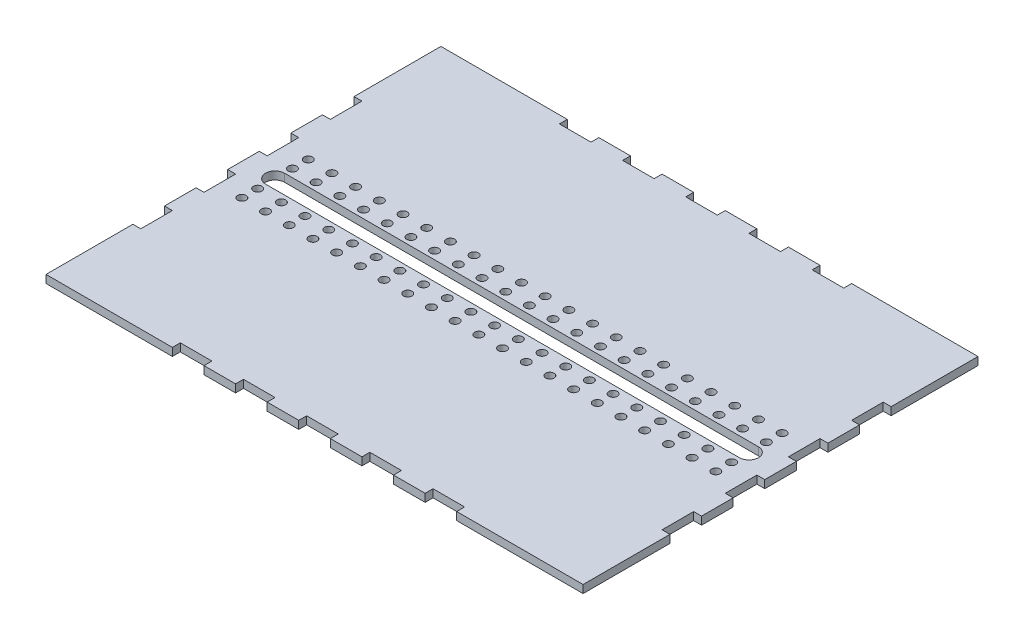
SolidWorks part; units mm, degrees
ref_plane "Front Plane" through (0, 0, 0) normal (0, 0, 1) x (1, 0, 0)
ref_plane "Top Plane" through (0, 0, 0) normal (0, 1, 0) x (1, 0, 0)
ref_plane "Right Plane" through (0, 0, 0) normal (1, 0, 0) x (0, 0, -1)
sketch "Sketch1" plane through (0, 0, 0) normal (0, 1, 0) x (1, 0, 0)
  line L0 (-14.0646, -39.6932) -> (-14.0646, 76.1041) construction
  line L3 (-122.0146, 89.7166) -> (-71.2146, 89.7166)
  line L5 (43.0854, -69.0334) -> (93.8854, -69.0334)
  line L6 (-122.0146, 89.7166) -> (93.8854, -69.0334) construction
  line L7 (-122.0146, 10.3416) -> (53.3287, 10.3416) construction
  line L8 (-20.4146, 89.7166) -> (-20.4146, 86.5416)
  line L9 (-20.4146, 86.5416) -> (-7.7146, 86.5416)
  line L10 (-7.7146, 86.5416) -> (-7.7146, 89.7166)
  line L11 (-33.1146, 89.7166) -> (-33.1146, 86.5416)
  line L12 (-33.1146, 86.5416) -> (-45.8146, 86.5416)
  line L13 (-45.8146, 86.5416) -> (-45.8146, 89.7166)
  line L14 (-58.5146, 89.7166) -> (-58.5146, 86.5416)
  line L15 (-58.5146, 86.5416) -> (-71.2146, 86.5416)
  line L16 (-71.2146, 86.5416) -> (-71.2146, 89.7166)
  line L17 (-58.5146, 89.7166) -> (-45.8146, 89.7166)
  line L18 (-33.1146, 89.7166) -> (-20.4146, 89.7166)
  line L19 (-7.7146, 89.7166) -> (4.9854, 89.7166)
  line L20 (4.9854, 89.7166) -> (4.9854, 86.5416)
  line L21 (4.9854, 86.5416) -> (17.6854, 86.5416)
  line L22 (17.6854, 86.5416) -> (17.6854, 89.7166)
  line L23 (30.3854, 89.7166) -> (30.3854, 86.5416)
  line L24 (30.3854, 86.5416) -> (43.0854, 86.5416)
  line L25 (43.0854, 86.5416) -> (43.0854, 89.7166)
  line L26 (17.6854, 89.7166) -> (30.3854, 89.7166)
  line L27 (43.0854, 89.7166) -> (93.8854, 89.7166)
  line L29 (-122.0146, 54.7916) -> (-118.8396, 54.7916)
  line L30 (-118.8396, 54.7916) -> (-118.8396, 42.0916)
  line L31 (-118.8396, 42.0916) -> (-122.0146, 42.0916)
  line L32 (-122.0146, 42.0916) -> (-122.0146, 29.3916)
  line L33 (-122.0146, 29.3916) -> (-118.8396, 29.3916)
  line L34 (-118.8396, 29.3916) -> (-118.8396, 16.6916)
  line L35 (-118.8396, 16.6916) -> (-122.0146, 16.6916)
  line L36 (-122.0146, 16.6916) -> (-122.0146, 3.9916)
  line L37 (-122.0146, 3.9916) -> (-118.8396, 3.9916)
  line L38 (-118.8396, 3.9916) -> (-118.8396, -8.7084)
  line L39 (-118.8396, -8.7084) -> (-122.0146, -8.7084)
  line L40 (-122.0146, -8.7084) -> (-122.0146, -21.4084)
  line L41 (-122.0146, -21.4084) -> (-118.8396, -21.4084)
  line L42 (-118.8396, -21.4084) -> (-118.8396, -34.1084)
  line L43 (-118.8396, -34.1084) -> (-122.0146, -34.1084)
  line L44 (-122.0146, -34.1084) -> (-122.0146, -69.0334)
  line L48 (-122.0146, 54.7916) -> (-122.0146, 89.7166)
  line L49 (17.6854, -69.0334) -> (30.3854, -69.0334)
  line L50 (43.0854, -65.8584) -> (43.0854, -69.0334)
  line L51 (30.3854, -65.8584) -> (43.0854, -65.8584)
  line L52 (30.3854, -69.0334) -> (30.3854, -65.8584)
  line L53 (17.6854, -65.8584) -> (17.6854, -69.0334)
  line L54 (4.9854, -65.8584) -> (17.6854, -65.8584)
  line L55 (4.9854, -69.0334) -> (4.9854, -65.8584)
  line L56 (-7.7146, -69.0334) -> (4.9854, -69.0334)
  line L57 (-33.1146, -69.0334) -> (-20.4146, -69.0334)
  line L58 (-58.5146, -69.0334) -> (-45.8146, -69.0334)
  line L59 (-71.2146, -65.8584) -> (-71.2146, -69.0334)
  line L60 (-58.5146, -65.8584) -> (-71.2146, -65.8584)
  line L61 (-58.5146, -69.0334) -> (-58.5146, -65.8584)
  line L62 (-45.8146, -65.8584) -> (-45.8146, -69.0334)
  line L63 (-33.1146, -65.8584) -> (-45.8146, -65.8584)
  line L64 (-33.1146, -69.0334) -> (-33.1146, -65.8584)
  line L65 (-7.7146, -65.8584) -> (-7.7146, -69.0334)
  line L66 (-20.4146, -65.8584) -> (-7.7146, -65.8584)
  line L67 (-20.4146, -69.0334) -> (-20.4146, -65.8584)
  line L68 (-122.0146, -69.0334) -> (-71.2146, -69.0334)
  line L69 (93.8854, 54.7916) -> (93.8854, 89.7166)
  line L70 (93.8854, -34.1084) -> (93.8854, -69.0334)
  line L71 (90.7104, -34.1084) -> (93.8854, -34.1084)
  line L72 (90.7104, -21.4084) -> (90.7104, -34.1084)
  line L73 (93.8854, -21.4084) -> (90.7104, -21.4084)
  line L74 (93.8854, -8.7084) -> (93.8854, -21.4084)
  line L75 (90.7104, -8.7084) -> (93.8854, -8.7084)
  line L76 (90.7104, 3.9916) -> (90.7104, -8.7084)
  line L77 (93.8854, 3.9916) -> (90.7104, 3.9916)
  line L78 (93.8854, 16.6916) -> (93.8854, 3.9916)
  line L79 (90.7104, 16.6916) -> (93.8854, 16.6916)
  line L80 (90.7104, 29.3916) -> (90.7104, 16.6916)
  line L81 (93.8854, 29.3916) -> (90.7104, 29.3916)
  line L82 (93.8854, 42.0916) -> (93.8854, 29.3916)
  line L83 (90.7104, 42.0916) -> (93.8854, 42.0916)
  line L84 (90.7104, 54.7916) -> (90.7104, 42.0916)
  line L85 (93.8854, 54.7916) -> (90.7104, 54.7916)
  point P0 (0, 0)
  dimension "D1" = 12.7
  dimension "D2" = 6.35
  dimension "D3" = 12.7
  dimension "D4" = 3.175
  dimension "D5" = 3.175
  dimension "D6" = 12.7
  dimension "D7" = 12.7
  dimension "D8" = 158.75
  dimension "D9" = 215.9
extrude "Boss-Extrude1" add sketch "Sketch1" along normal mid plane 3.175
sketch "Sketch2" plane through (0, 1.5875, 0) normal (0, 1, 0) x (1, 0, 0)
  line L0 (93.8854, 10.3416) -> (-122.0146, 10.3416) construction
  line L1 (93.8854, 3.9916) -> (93.8854, 16.6916) construction
  line L2 (-122.0146, 16.6916) -> (-122.0146, 3.9916) construction
  line L3 (-14.0646, -69.0334) -> (-14.0646, 89.7166) construction
  line L4 (-20.4146, -69.0334) -> (-7.7146, -69.0334) construction
  line L5 (-20.4146, 89.7166) -> (-7.7146, 89.7166) construction
  line L6 (81.1854, 10.3416) -> (-109.3146, 10.3416) construction
  line L7 (81.1854, 6.5316) -> (-109.3146, 6.5316)
  line L8 (81.1854, 14.1516) -> (-109.3146, 14.1516)
  arc A0 (81.1854, 6.5316) -> (81.1854, 14.1516) centre (81.1854, 10.3416) ccw
  arc A1 (-109.3146, 14.1516) -> (-109.3146, 6.5316) centre (-109.3146, 10.3416) ccw
  point P14 (-14.0646, 10.3416)
  dimension "D2" = 190.5
  dimension "D1" = 7.62
  dimension "D3" = 0
extrude "Cut-Extrude1" cut sketch "Sketch2" against normal through all
sketch "Sketch3" plane through (0, 1.5875, 0) normal (0, 1, 0) x (1, 0, 0)
  circle A0 centre (-109.3146, 23.6766) radius 1.7018
  circle A1 centre (-109.3146, 17.3266) radius 1.7018
  dimension "D1" = 3.4036
extrude "Cut-Extrude2" cut sketch "Sketch3" against normal through all
pattern_linear "LPattern1" count 21 spacing 9.525 along (1, 0, 0) of "Cut-Extrude2"
ref_plane "Plane1" through (0, 0, -10.3416) normal (0, 0, 1) x (1, 0, 0)
mirror "Mirror1" about plane through (0, 0, -10.3416) normal (0, 0, 1) of "LPattern1"
